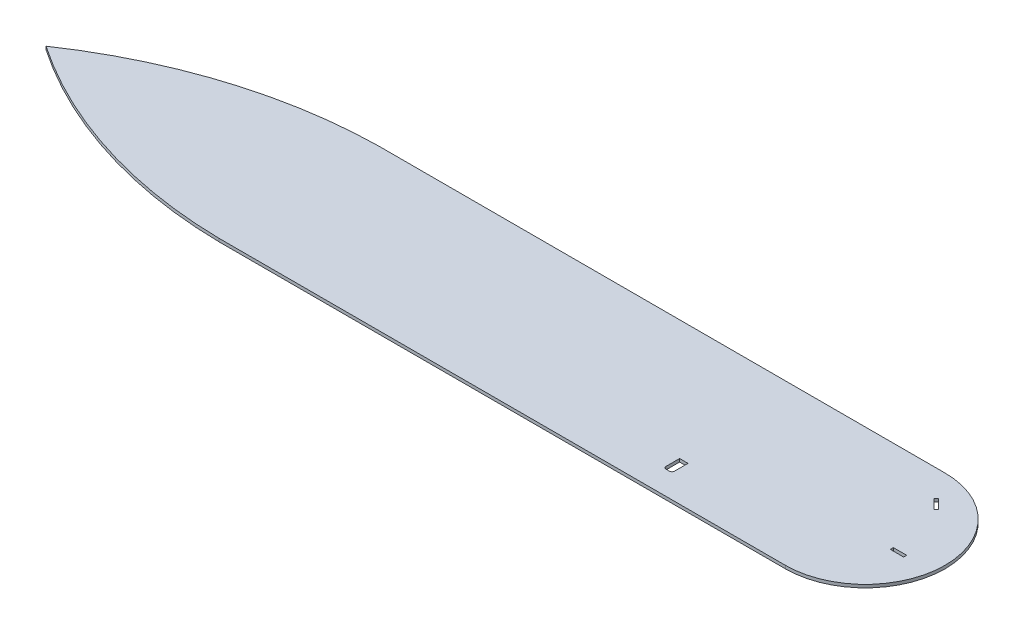
SolidWorks part; units mm, degrees
ref_plane "Front Plane" through (0, 0, 0) normal (0, 0, 1) x (1, 0, 0)
ref_plane "Top Plane" through (0, 0, 0) normal (0, 1, 0) x (1, 0, 0)
ref_plane "Right Plane" through (0, 0, 0) normal (1, 0, 0) x (0, 0, -1)
sketch "Sketch1" plane through (0, 0, 0) normal (0, 1, 0) x (1, 0, 0)
  line L0 (800, 78) -> (0, 78) construction
  line L1 (247.0699, 0) -> (800, 0)
  line L2 (0, 0) -> (0, 156) construction
  line L3 (247.0699, 156) -> (800, 156)
  arc A0 (800, 156) -> (800, 0) centre (800, 78) cw
  arc A1 (247.0699, 156) -> (0, 78) centre (253.6132, -295.0311) ccw
  arc A2 (247.0699, 0) -> (0, 78) centre (253.6132, 451.0311) cw
  dimension "D1" = 800
  dimension "D2" = 156
  dimension "D3" = 247.0699
extrude "Boss-Extrude1" add sketch "Sketch1" along normal blind 3
sketch "Sketch2" plane through (0, 0, 0) normal (0, -1, 0) x (1, 0, 0)
  line L4 (825.4003, -119.7208) -> (816.2079, -128.9132)
  line L5 (816.2079, -128.9132) -> (818.3292, -131.0345)
  line L6 (818.3292, -131.0345) -> (827.5216, -121.8421)
  line L7 (827.5216, -121.8421) -> (825.4003, -119.7208)
  line L8 (825.4003, -119.7208) -> (816.2079, -128.9132)
  line L9 (816.2079, -128.9132) -> (818.3292, -131.0345)
  line L10 (818.3292, -131.0345) -> (827.5216, -121.8421)
  line L11 (827.5216, -121.8421) -> (825.4003, -119.7208)
  line L28 (850.755, -64.6967) -> (837.755, -64.6967)
  line L29 (837.755, -64.6967) -> (837.755, -67.6967)
  line L30 (837.755, -67.6967) -> (850.755, -67.6967)
  line L31 (850.755, -67.6967) -> (850.755, -64.6967)
  line L32 (850.755, -64.6967) -> (837.755, -64.6967)
  line L33 (837.755, -64.6967) -> (837.755, -67.6967)
  line L34 (837.755, -67.6967) -> (850.755, -67.6967)
  line L35 (850.755, -67.6967) -> (850.755, -64.6967)
  line L40 (658.0699, -25.4734) -> (658.0699, -38.6734)
  line L41 (663.7699, -22.9734) -> (660.5699, -22.9734)
  line L42 (666.2699, -38.6734) -> (666.2699, -25.4734)
  line L43 (658.0699, -38.6734) -> (666.2699, -38.6734)
  line L44 (658.0699, -25.4734) -> (658.0699, -38.6734)
  line L45 (663.7699, -22.9734) -> (660.5699, -22.9734)
  line L46 (666.2699, -38.6734) -> (666.2699, -25.4734)
  line L47 (658.0699, -38.6734) -> (666.2699, -38.6734)
  arc A2 (660.5699, -22.9734) -> (658.0699, -25.4734) centre (660.5699, -25.4734) ccw
  arc A3 (666.2699, -25.4734) -> (663.7699, -22.9734) centre (663.7699, -25.4734) ccw
  arc A4 (660.5699, -22.9734) -> (658.0699, -25.4734) centre (660.5699, -25.4734) ccw
  arc A5 (666.2699, -25.4734) -> (663.7699, -22.9734) centre (663.7699, -25.4734) ccw
  dimension "D1" = 0
  dimension "D2" = 0
  dimension "D3" = 0
extrude "Cut-Extrude1" cut sketch "Sketch2" against normal through all
